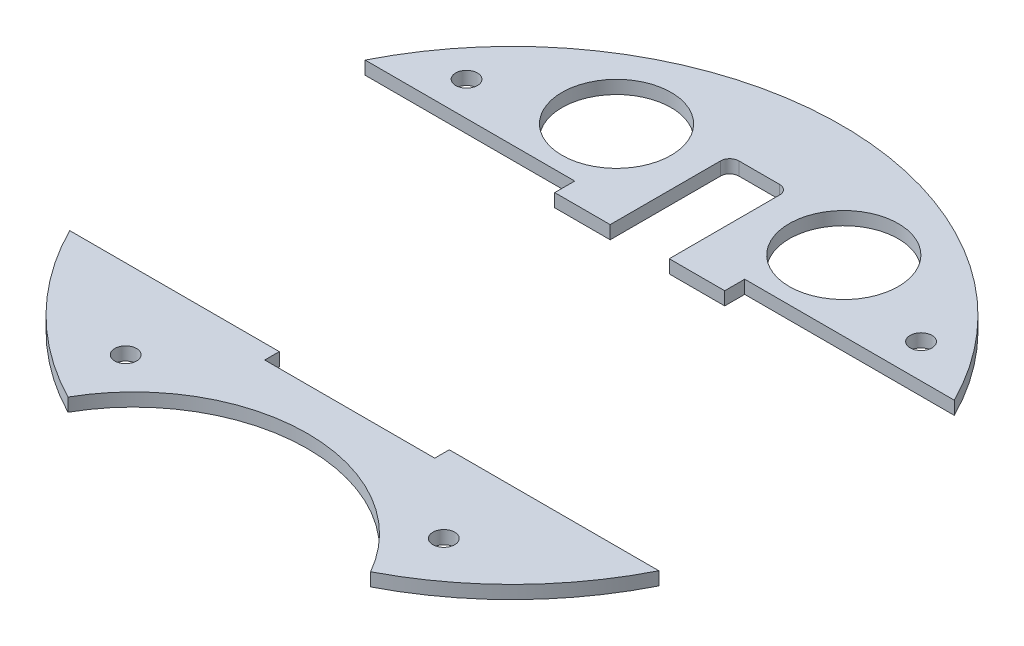
SolidWorks part; units mm, degrees
material "Acrylic (Medium-high impact)"
ref_plane "Front Plane" through (0, 0, 0) normal (0, 0, 1) x (1, 0, 0)
ref_plane "Top Plane" through (0, 0, 0) normal (0, 1, 0) x (1, 0, 0)
ref_plane "Right Plane" through (0, 0, 0) normal (1, 0, 0) x (0, 0, -1)
sketch "Sketch1" plane through (0, 0, 0) normal (0, 1, 0) x (1, 0, 0)
  line L0 (0, -83.2398) -> (-33.2911, -64.4046) construction
  line L1 (0, -83.2398) -> (0, 0) construction
  arc A0 (33.2911, -64.4046) -> (-33.2911, -64.4046) centre (0, 0) ccw
  arc A1 (33.2911, -64.4046) -> (-33.2911, -64.4046) centre (0, -83.2398) ccw
  dimension "D1" = 145
  dimension "D2" = 76.5
  dimension "D3" = 60.5
extrude "Boss-Extrude1" add sketch "Sketch1" along normal blind 2.9
sketch "solenoid placement" plane through (0, 2.9, 0) normal (0, 1, 0) x (1, 0, 0)
  line L4 (-18.7, -35.7) -> (18.7, -35.7)
  line L5 (18.7, -35.7) -> (18.7, 28.1)
  line L6 (18.7, 28.1) -> (-18.7, 28.1)
  line L7 (-18.7, 28.1) -> (-18.7, -35.7)
  line L8 (-18.7, -35.7) -> (18.7, -35.7)
  line L9 (18.7, -35.7) -> (18.7, 28.1)
  line L10 (18.7, 28.1) -> (-18.7, 28.1)
  line L11 (-18.7, 28.1) -> (-18.7, -35.7)
  circle A1 centre (0, 0) radius 72.5 construction
  arc A2 (33.2911, -64.4046) -> (-33.2911, -64.4046) centre (0, 0) ccw construction
  dimension "D1" = 0
extrude "Cut-Extrude1" cut sketch "solenoid placement" against normal through all
sketch "Sketch4" plane through (0, 2.9, 0) normal (0, 1, 0) x (1, 0, 0)
  line L0 (18.7, 28.1) -> (-18.7, 28.1) construction
  line L1 (-6.5, 28.1) -> (6.5, 28.1)
  line L2 (-6.5, 28.1) -> (-6.5, 52.4)
  line L3 (6.5, 54.4) -> (-6.5, 54.4) construction
  line L4 (6.5, 28.1) -> (6.5, 52.4)
  line L5 (4.5, 54.4) -> (-4.5, 54.4)
  arc A0 (4.5, 54.4) -> (6.5, 52.4) centre (4.5, 52.4) cw
  arc A1 (-4.5, 54.4) -> (-6.5, 52.4) centre (-4.5, 52.4) ccw
  point P6 (0, 28.1)
  dimension "D1" = 2
extrude "Cut-Extrude4" cut sketch "Sketch4" against normal through all
sketch "Sketch5" plane through (0, 2.9, 0) normal (0, 1, 0) x (1, 0, 0)
  circle A2 centre (-25, 48) radius 12
  circle A3 centre (-25, 48) radius 12
  circle A4 centre (25, 48) radius 12
  circle A21 centre (25, 48) radius 12
  dimension "D1" = 0
  dimension "D2" = 0
extrude "Cut-Extrude5" cut sketch "Sketch5" against normal through all
sketch "Sketch6" plane through (0, 2.9, 0) normal (0, 1, 0) x (1, 0, 0)
  circle A1 centre (35, -50) radius 2.4
  circle A2 centre (35, -50) radius 2.4
  circle A3 centre (-35, -50) radius 2.4
  circle A4 centre (-35, -50) radius 2.4
  circle A5 centre (-50, 40) radius 2.4
  circle A6 centre (-50, 40) radius 2.4
  circle A7 centre (50, 40) radius 2.4
  circle A8 centre (50, 40) radius 2.4
  dimension "D1" = 0
  dimension "D2" = 0
  dimension "D3" = 0
  dimension "D4" = 0
extrude "Cut-Extrude6" cut sketch "Sketch6" against normal through all
sketch "Sketch3" plane through (0, 2.9, 0) normal (0, 1, 0) x (1, 0, 0)
  line L0 (-18.7, 28.1) -> (18.7, 28.1)
  line L1 (-72.5, -32.5) -> (72.5, -32.5)
  line L2 (-72.5, -32.5) -> (-72.5, 32.5)
  line L3 (-72.5, 32.5) -> (-18.7, 32.5)
  line L4 (72.5, -32.5) -> (72.5, 32.5)
  line L5 (-72.5, -32.5) -> (72.5, 32.5) construction
  line L6 (-72.5, 32.5) -> (72.5, -32.5) construction
  line L7 (18.7, 28.1) -> (18.7, 32.5)
  line L8 (-18.7, 28.1) -> (-18.7, 32.5)
  line L9 (18.7, 32.5) -> (72.5, 32.5)
  arc A0 (33.2911, -64.4046) -> (-33.2911, -64.4046) centre (0, 0) ccw construction
  point P0 (0, 0)
  dimension "D1" = 65
extrude "Cut-Extrude3" cut sketch "Sketch3" against normal through all
equation "\"smallPulleyTeeth\"= 15"
equation "\"largePulleyTeeth\"= 30"
equation "\"eighthThick\"= 2.9mm"
equation "\"sixteenthThick\" = 1.7mm"
equation "\"quarterThick\"=6.0mm"
equation "\"OD\" = 145mm"
equation "\"puckAngle\" = 60.5deg"
equation "\"D1@Sketch1\"=\"OD\""
equation "\"puckDiam\" = 76.5mm"
equation "\"D2@Sketch1\"=\"puckDiam\""
equation "\"D3@Sketch1\"=\"puckAngle\""
equation "\"D1@Boss-Extrude1\"=\"eighthThick\""
equation "\"axlePress\" = 5.9mm"
equation "\"press\" = 0.2mm"
equation "\"wheelClear\" = 0.3mm"
equation "\"10-32clear\" = 4.8mm"
equation "\"6-32clear\" = 3.3mm"
equation "\"8-32clear\" = 4.0mm"
equation "\"wheelHeight\" = 22mm"
equation "\"wheelWell\" = 65mm"
equation "\"D1@Sketch3\"=\"wheelWell\""
